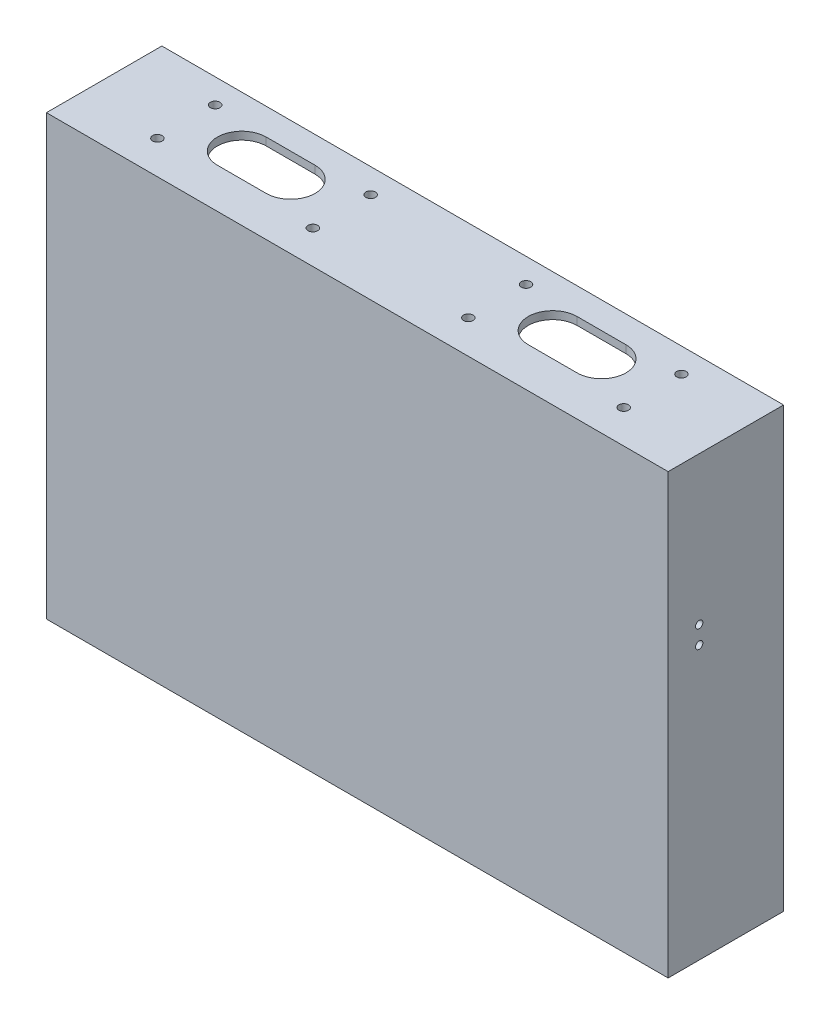
SolidWorks part; units mm, degrees
ref_plane "Front Plane" through (0, 0, 0) normal (0, 0, 1) x (1, 0, 0)
ref_plane "Top Plane" through (0, 0, 0) normal (0, 1, 0) x (1, 0, 0)
ref_plane "Right Plane" through (0, 0, 0) normal (1, 0, 0) x (0, 0, -1)
ref_plane "Plane1" through (0, 198, 0) normal (0, -1, 0) x (1, 0, 0)
sketch "Sketch1" plane through (0, 198, 0) normal (0, -1, 0) x (1, 0, 0)
  line L0 (0, 9) -> (280, 9)
  line L1 (280, 9) -> (280, 61)
  line L2 (280, 61) -> (0, 61)
  line L3 (0, 61) -> (0, 9)
extrude "Placa" add sketch "Sketch1" against normal blind 3.5
sketch "Sketch2" plane through (0, 198, 0) normal (0, -1, 0) x (1, 0, 0)
  line L0 (271.25, 9) -> (271.25, 17)
  line L1 (271.25, 17) -> (277, 22.75)
  line L2 (277, 22.75) -> (277, 58)
  line L3 (277, 58) -> (141.5, 58)
  line L4 (141.5, 58) -> (141.5, 24.25)
  line L5 (141.5, 24.25) -> (148.75, 17)
  line L6 (148.75, 17) -> (148.75, 9)
  line L7 (148.75, 9) -> (131.25, 9)
  line L8 (131.25, 9) -> (131.25, 17)
  line L9 (131.25, 17) -> (138.5, 24.25)
  line L10 (138.5, 24.25) -> (138.5, 58)
  line L11 (138.5, 58) -> (3, 58)
  line L12 (3, 58) -> (3, 22.75)
  line L13 (3, 22.75) -> (8.75, 17)
  line L14 (8.75, 17) -> (8.75, 9)
  line L15 (8.75, 9) -> (0, 9)
  line L16 (0, 9) -> (0, 61)
  line L17 (0, 61) -> (280, 61)
  line L18 (280, 61) -> (280, 9)
  line L19 (280, 9) -> (271.25, 9)
extrude "Venas apoyo" add sketch "Sketch2" along normal blind 191
sketch "Sketch3" plane through (0, 7, 0) normal (0, -1, 0) x (1, 0, 0)
  line L0 (0, 61) -> (280, 61)
  line L1 (280, 61) -> (280, 9)
  line L2 (280, 9) -> (0, 9)
  line L3 (0, 9) -> (0, 61)
extrude "Tapa exterior" add sketch "Sketch3" along normal blind 3
sketch "Sketch8" plane through (141.5, 0, 0) normal (1, 0, 0) x (0, 0, -1)
  line L0 (-55, 156) -> (-55, 142)
  line L1 (-29, 142) -> (-29, 156)
  line L2 (-58, 7) -> (-58, 198) construction
  line L3 (-24.25, 198) -> (-58, 198) construction
  line L4 (-58, 102.5) -> (-24.25, 102.5) construction
  line L5 (-24.25, 7) -> (-24.25, 198) construction
  line L6 (-55, 49) -> (-55, 63)
  line L7 (-29, 63) -> (-29, 49)
  arc A0 (-55, 142) -> (-29, 142) centre (-42, 142) ccw
  arc A1 (-29, 156) -> (-55, 156) centre (-42, 156) ccw
  arc A2 (-55, 63) -> (-29, 63) centre (-42, 63) cw
  arc A3 (-29, 49) -> (-55, 49) centre (-42, 49) cw
  point P8 (-42, 169)
  dimension "D2" = 13
  dimension "D1" = 3
  dimension "D3" = 14
  dimension "D4" = 29
extrude "Cut-Extrude3" cut sketch "Sketch8" against normal up to next
sketch "Sketch9" plane through (0, 198, 0) normal (0, -1, 0) x (1, 0, 0)
  line L0 (221, 43) -> (199, 43)
  line L1 (199, 21) -> (221, 21)
  line L2 (280, 61) -> (0, 61) construction
  line L3 (210, 9) -> (210, 58.0057) construction
  line L4 (148.75, 9) -> (271.25, 9) construction
  line L6 (81, 43) -> (59, 43)
  line L7 (59, 21) -> (81, 21)
  arc A0 (199, 43) -> (199, 21) centre (199, 32) ccw
  arc A1 (221, 21) -> (221, 43) centre (221, 32) ccw
  arc A2 (59, 43) -> (59, 21) centre (59, 32) ccw
  arc A3 (81, 21) -> (81, 43) centre (81, 32) ccw
  point P12 (210, 21)
  dimension "D2" = 11
  dimension "D1" = 18
  dimension "D3" = 22
  dimension "D4" = 2
extrude "Pasacables entre cajas" cut sketch "Sketch9" against normal through all
hole_wizard "Ø2.5 (3) Diameter Hole1" positions "Sketch13" profile "Sketch12" hole size "Ø2.5" standard "ANSI Metric"
sketch "Sketch13" plane through (0, 0, 9) normal (0, 0, -1) x (-1, 0, 0)
  point P0 (-275.5, 187)
  point P1 (-275.5, 165)
  point P2 (-144.5, 187)
  point P3 (-144.5, 165)
  point P4 (-275.5, 143)
  point P5 (-275.5, 121)
  point P6 (-144.5, 143)
  point P7 (-144.5, 121)
  point P8 (-135.5, 187)
  point P9 (-135.5, 165)
  point P10 (-4.5, 187)
  point P11 (-4.5, 165)
  point P12 (-135.5, 143)
  point P13 (-135.5, 121)
  point P14 (-4.5, 143)
  point P15 (-4.5, 121)
  point P16 (-275.5, 99)
  point P17 (-275.5, 77)
  point P18 (-275.5, 55)
  point P19 (-144.5, 99)
  point P20 (-144.5, 77)
  point P21 (-144.5, 55)
  point P22 (-275.5, 33)
  point P23 (-275.5, 11)
  point P24 (-144.5, 33)
  point P25 (-144.5, 11)
  point P26 (-135.5, 99)
  point P27 (-135.5, 77)
  point P28 (-135.5, 55)
  point P29 (-4.5, 99)
  point P30 (-4.5, 77)
  point P31 (-4.5, 55)
  point P32 (-135.5, 33)
  point P33 (-135.5, 11)
  point P34 (-4.5, 33)
  point P35 (-4.5, 11)
sketch "Sketch12" plane through (275.5, 187, 9) normal (1, 0, 0) x (0, 1, 0)
  line L0 (0, 0) -> (0, 10)
  line L1 (0, 10) -> (1.5, 10)
  line L2 (1.5, 10) -> (1.5, 0)
  line L5 (1.5, 0) -> (0, 0)
  line L10 (0, 10) -> (-1.5, 10) construction
  line L11 (0, -6.35) -> (0, 107.95) construction
  dimension "Hole Dia." = 3
  dimension "Hole Depth" = 10
  dimension "Drill Angle" = 180
hole_wizard "Ø4.3 (4.3) Diameter Hole1" positions "Sketch15" profile "Sketch14" hole size "Ø4.3" standard "ANSI Metric" end condition up to next
sketch "Sketch15" plane through (0, 201.5, 0) normal (0, 1, 0) x (1, 0, 0)
  point P0 (245, -46)
  point P1 (175, -46)
  point P2 (245, -20)
  point P3 (175, -20)
  point P4 (105, -46)
  point P5 (35, -46)
  point P6 (105, -20)
  point P7 (35, -20)
sketch "Sketch14" plane through (245, 201.5, 46) normal (1, 0, 0) x (0, 0, 1)
  line L0 (0, 0) -> (0, 3.5)
  line L1 (0, 3.5) -> (2.15, 3.5)
  line L2 (2.15, 3.5) -> (2.15, 0)
  line L5 (2.15, 0) -> (0, 0)
  line L11 (0, -6.35) -> (0, 107.95) construction
  dimension "Thru Hole Dia." = 4.3
  dimension "Thru Hole Depth" = 3.5
sketch "Sketch18" plane through (0, 0, 0) normal (-1, 0, 0) x (0, 0, 1)
  line L0 (39.0586, 39.3672) -> (51.5586, 39.3672)
  line L1 (40.0586, 38.3672) -> (50.5586, 38.3672) construction
  line L2 (40.0586, 38.3672) -> (40.0586, 26.3672) construction
  line L3 (40.0586, 26.3672) -> (50.5586, 26.3672) construction
  line L4 (50.5586, 38.3672) -> (50.5586, 26.3672) construction
  line L5 (51.5586, 39.3672) -> (51.5586, 25.3672)
  line L6 (39.0586, 25.3672) -> (51.5586, 25.3672)
  line L7 (39.0586, 39.3672) -> (39.0586, 25.3672)
  circle A0 centre (48.8464, 69.6645) radius 1.8
  dimension "D2" = 3.6
  dimension "D1" = 1
extrude "Cut-Extrude5" cut sketch "Sketch18" against normal up to next
sketch "Sketch19" plane through (0, 0, 58) normal (0, 0, -1) x (-1, 0, 0)
  line L0 (0, 201.5) -> (0, 4) construction
  line L1 (0, 4) -> (-280, 4) construction
  circle A0 centre (-67.205, 76.283) radius 3
  circle A1 centre (-67.205, 20.674) radius 3
  circle A2 centre (-7.81, 76.283) radius 3
  circle A3 centre (-7.81, 20.674) radius 3
  circle A4 centre (-67.205, 76.283) radius 1.6
  circle A5 centre (-7.81, 76.283) radius 1.6
  circle A6 centre (-7.81, 20.674) radius 1.6
  circle A7 centre (-67.205, 20.674) radius 1.6
  circle A8 centre (-96.5374, 88.9169) radius 3
  circle A9 centre (-96.5374, 88.9169) radius 1.6
  circle A10 centre (-42.3084, 88.9169) radius 3
  circle A11 centre (-42.3084, 88.9169) radius 1.6
  circle A12 centre (-42.3084, 125.2229) radius 3
  circle A13 centre (-42.3084, 125.2229) radius 1.6
  circle A14 centre (-96.5374, 125.2229) radius 3
  circle A15 centre (-96.5374, 125.2229) radius 1.6
  circle A16 centre (-96.5374, 148.2134) radius 3
  circle A17 centre (-96.5374, 148.2134) radius 1.6
  circle A18 centre (-42.3084, 148.2134) radius 3
  circle A19 centre (-42.3084, 148.2134) radius 1.6
  circle A20 centre (-42.3084, 184.5194) radius 3
  circle A21 centre (-42.3084, 184.5194) radius 1.6
  circle A22 centre (-96.5374, 184.5194) radius 3
  circle A23 centre (-96.5374, 184.5194) radius 1.6
  circle A24 centre (-184.6933, 175.46) radius 3
  circle A25 centre (-184.6933, 175.46) radius 1.6
  circle A26 centre (-184.6933, 139.154) radius 3
  circle A27 centre (-184.6933, 139.154) radius 1.6
  circle A28 centre (-238.9223, 139.154) radius 3
  circle A29 centre (-238.9223, 139.154) radius 1.6
  circle A30 centre (-238.9223, 175.46) radius 3
  circle A31 centre (-238.9223, 175.46) radius 1.6
  circle A32 centre (-238.9223, 88.1735) radius 3
  circle A33 centre (-238.9223, 88.1735) radius 1.6
  circle A34 centre (-184.6933, 88.1735) radius 3
  circle A35 centre (-184.6933, 88.1735) radius 1.6
  circle A36 centre (-184.6933, 51.8675) radius 3
  circle A37 centre (-184.6933, 51.8675) radius 1.6
  circle A38 centre (-238.9223, 51.8675) radius 3
  circle A39 centre (-238.9223, 51.8675) radius 1.6
  dimension "D1" = 6
  dimension "D2" = 3.2
  dimension "D3" = 67.205
  dimension "D4" = 72.283
  dimension "D5" = 59.395
  dimension "D6" = 55.609
extrude "Boss-Extrude2" add sketch "Sketch19" along normal blind 5
fillet "Fillet1" radius 3 20 edges at (10.81, 20.674, 58) (10.81, 76.283, 58) (70.205, 76.283, 58) (70.205, 20.674, 58) (241.9223, 88.1735, 58) (187.6933, 88.1735, 58) (187.6933, 51.8675, 58) (241.9223, 51.8675, 58) (241.9223, 175.46, 58) (241.9223, 139.154, 58) (187.6933, 175.46, 58) (187.6933, 139.154, 58) (45.3084, 184.5194, 58) (99.5374, 184.5194, 58) (45.3084, 88.9169, 58) (99.5374, 148.2134, 58) (45.3084, 148.2134, 58) (45.3084, 125.2229, 58) (99.5374, 88.9169, 58) (99.5374, 125.2229, 58)
sketch "Sketch20" plane through (0, 0, 0) normal (-1, 0, 0) x (0, 0, 1)
  circle A0 centre (47, 134.8568) radius 1.65
  circle A1 centre (47, 126.8568) radius 1.65
  dimension "D1" = 3.3
extrude "Cut-Extrude6" cut sketch "Sketch20" against normal through all
